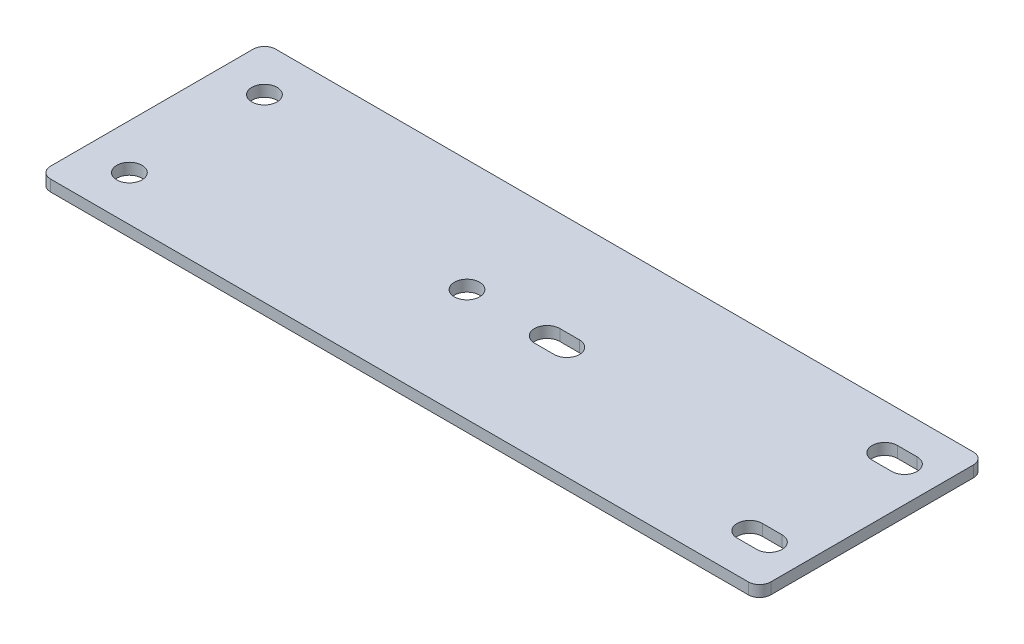
SolidWorks part; units mm, degrees
ref_plane "Front Plane" through (0, 0, 0) normal (0, 0, 1) x (1, 0, 0)
ref_plane "Top Plane" through (0, 0, 0) normal (0, 1, 0) x (1, 0, 0)
ref_plane "Right Plane" through (0, 0, 0) normal (1, 0, 0) x (0, 0, -1)
sketch "Sketch1" plane through (0, 0, 0) normal (0, 1, 0) x (1, 0, 0)
  line L1 (0, 0) -> (203.2, 0)
  line L2 (0, 0) -> (0, 63.5)
  line L3 (0, 63.5) -> (203.2, 63.5)
  line L4 (203.2, 0) -> (203.2, 63.5)
  dimension "D1" = 63.5
  dimension "D2" = 203.2
extrude "Boss-Extrude1" add sketch "Sketch1" along normal blind 3.175
hole_wizard "9/32 (0.28125) Diameter Hole1" positions "Sketch2" profile "Sketch3" hole size "9/32" standard "ANSI Inch" end condition through all
sketch "Sketch2" plane through (0, 3.175, 0) normal (0, 1, 0) x (1, 0, 0)
  line L0 (0, 63.5) -> (0, 0) construction
  line L1 (0, 0) -> (203.2, 0) construction
  line L2 (203.2, 63.5) -> (0, 63.5) construction
  point P0 (12.7, 12.7)
  point P2 (12.7, 50.8)
  point P4 (88.9, 31.75)
  point P21 (0, 31.75)
  dimension "D1" = 88.9
  dimension "D2" = 12.7
  dimension "D3" = 12.7
sketch "Sketch3" plane through (12.7, 3.175, -12.7) normal (1, 0, 0) x (0, 0, 1)
  line L0 (0, 0) -> (0, 3.175)
  line L1 (0, 3.175) -> (3.5719, 3.175)
  line L2 (3.5719, 3.175) -> (3.5719, 0)
  line L5 (3.5719, 0) -> (0, 0)
  line L11 (0, -6.35) -> (0, 107.95) construction
  dimension "Thru Hole Dia." = 7.1437
  dimension "Thru Hole Depth" = 3.175
hole_wizard "9/32 (0.28125) Diameter Slot1" positions "Sketch4" profile "Sketch5" size "9/32" standard "ANSI Inch" slot yes end condition through all
sketch "Sketch4" plane through (0, 3.175, 0) normal (0, 1, 0) x (1, 0, 0)
  line L0 (107.95, 31.75) -> (120.65, 31.75) construction
  line L1 (203.2, 0) -> (203.2, 63.5) construction
  line L2 (203.2, 63.5) -> (0, 63.5) construction
  line L3 (0, 0) -> (203.2, 0) construction
  point P0 (114.3, 31.75)
  point P4 (190.5, 50.8)
  point P6 (190.5, 12.7)
  point P12 (203.2, 31.75)
  dimension "D1" = 12.7
  dimension "D2" = 12.7
  dimension "D3" = 12.7
  dimension "D4" = 88.9
  dimension "D5" = 12.7
  dimension "D6" = 12.7
sketch "Sketch5" plane through (114.3, 3.175, -31.75) normal (1, 0, 0) x (0, 0, 1)
  line L0 (0, 0) -> (0, 3.175)
  line L1 (0, 3.175) -> (3.5719, 3.175)
  line L2 (3.5719, 3.175) -> (3.5719, 0)
  line L5 (3.5719, 0) -> (0, 0)
  line L11 (0, -6.35) -> (0, 107.95) construction
  dimension "Thru Hole Dia." = 7.1437
  dimension "Thru Hole Depth" = 3.175
fillet "Fillet1" radius 3.175 4 edges at (0, 1.5875, -63.5) (0, 1.5875, 0) (203.2, 1.5875, -63.5) (203.2, 1.5875, 0)
